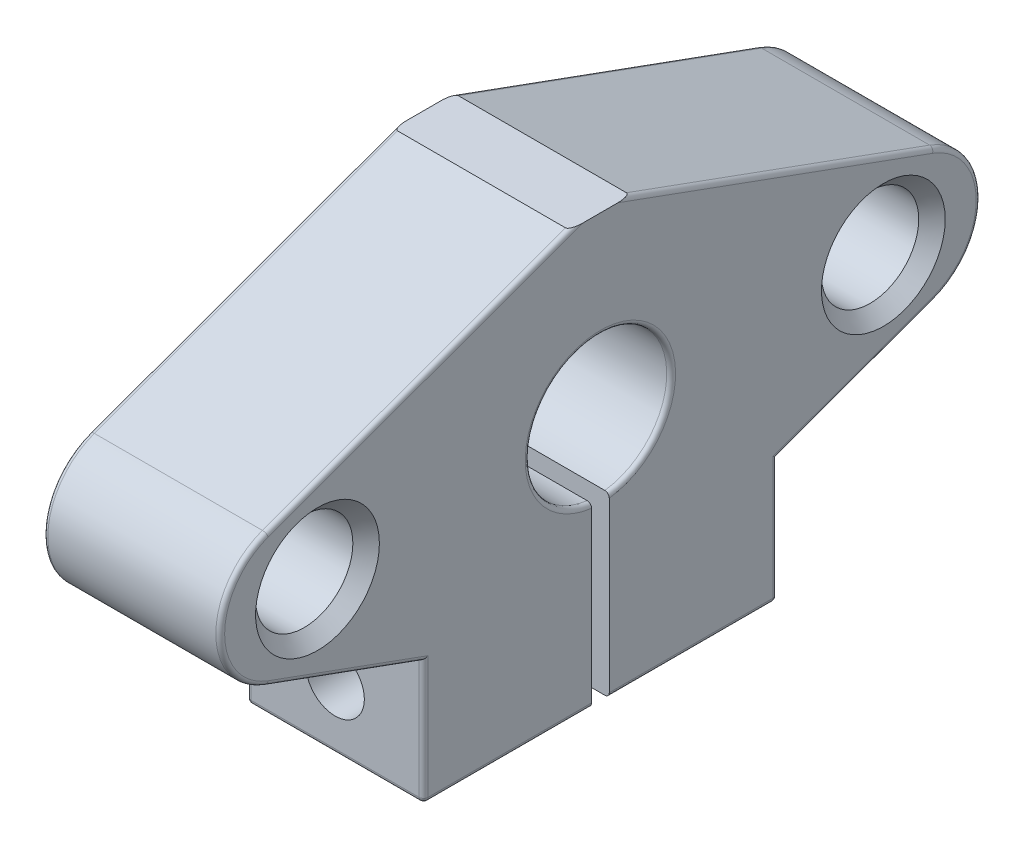
SolidWorks part; units mm, degrees
ref_plane "Plano frontal" through (0, 0, 0) normal (0, 0, 1) x (1, 0, 0)
ref_plane "Plano superior" through (0, 0, 0) normal (0, 1, 0) x (1, 0, 0)
ref_plane "Plano direito" through (0, 0, 0) normal (1, 0, 0) x (0, 0, -1)
sketch "Esboço1" plane through (0, 0, 0) normal (1, 0, 0) x (0, 0, -1)
  line L0 (0, 51.135) -> (0, -31.3516) construction
  line L1 (-77.457, 0) -> (113.3353, 0) construction
  line L2 (1.7204, 24) -> (18.8681, 17.7588)
  line L3 (18.8681, 10.2412) -> (10, 7.0135)
  line L4 (10, 7.0135) -> (10, 0)
  line L5 (-1.7204, 24) -> (1.7204, 24)
  line L6 (21.5, 14) -> (21.5, 29.1302) construction
  line L7 (10, 0) -> (-10, 0)
  line L8 (-1.7204, 24) -> (-18.8681, 17.7588)
  line L9 (-18.8681, 10.2412) -> (-10, 7.0135)
  line L10 (-10, 7.0135) -> (-10, 0)
  circle A0 centre (16, 14) radius 3.5 construction
  arc A1 (18.8681, 17.7588) -> (18.8681, 10.2412) centre (17.5, 14) cw
  arc A2 (-18.8681, 17.7588) -> (-18.8681, 10.2412) centre (-17.5, 14) ccw
  point P18 (0, 24)
  point P23 (0, 0)
  dimension "D3" = 7
  dimension "D4" = 24
  dimension "D7" = 4
  dimension "D1" = 10
  dimension "D2" = 16
  dimension "D5" = 21.5
  dimension "D6" = 40
  dimension "D8" = 10
  dimension "D9" = 10
extrude "Ressalto-extrusão1" add sketch "Esboço1" against normal blind 10
sketch "Esboço2" plane through (0, 0, 0) normal (1, 0, 0) x (0, 0, -1)
  line L0 (0, 28.9047) -> (0, -3.0339) construction
  line L1 (-30.4241, 14) -> (31.1368, 14) construction
  line L2 (-0.5, 10.0314) -> (-0.5, -0.626)
  line L3 (0.5, 10.0314) -> (0.5, -0.626)
  line L4 (-0.5, -0.626) -> (0.5, -0.626)
  arc A0 (0.5, 10.0314) -> (-0.5, 10.0314) centre (0, 14) ccw
  dimension "D1" = 8
  dimension "D2" = 0.5
  dimension "D3" = 0.5
extrude "Corte-extrusão1" cut sketch "Esboço2" against normal blind 10
hole_wizard "Escareado para parafuso de máquina com cabeça chata de M51" positions "Esboço6" profile "Esboço4" countersink size "M5" standard "Ansi Metric" end condition through all
sketch "Esboço6" plane through (0, 0, 0) normal (1, 0, 0) x (0, 0, -1)
  line L0 (0, 14) -> (38.7782, 13.8486) construction
  arc A0 (-18.8681, 17.7588) -> (-18.8681, 10.2412) centre (-17.5, 14) ccw construction
  arc A1 (18.8681, 10.2412) -> (18.8681, 17.7588) centre (17.5, 14) ccw construction
  point P0 (-16, 14.0625)
  point P2 (16, 13.9375)
  point P5 (-21.5, 14)
  point P9 (21.5, 14)
  dimension "D1" = 5.5
  dimension "D2" = 5.5
  dimension "D3" = 0
  dimension "D4" = 0
sketch "Esboço4" plane through (0, 14.0625, 16) normal (0, 1, 0) x (0, 0, -1)
  line L0 (0, 0) -> (0, 10)
  line L1 (0, 10) -> (2.75, 10)
  line L2 (2.75, 10) -> (2.75, 0.75)
  line L3 (2.75, 0.75) -> (3.5, 0)
  line L5 (3.5, 0) -> (0, 0)
  line L6 (-2.75, 0.75) -> (-3.5, 0) construction
  line L11 (0, -6.35) -> (0, 107.95) construction
  dimension "Thru Hole Dia." = 5.5
  dimension "Thru Hole Depth" = 10
  dimension "Near C'Sink Dia." = 7
  dimension "Near C'Sink Angle" = 90
sketch "Esboço7" plane through (0, 0, -10) normal (0, 0, -1) x (-1, 0, 0)
  line L0 (0, 3.5068) -> (10, 3.5068) construction
  line L1 (10, 0) -> (10, 7.0135) construction
  line L2 (0, 0) -> (0, 7.0135) construction
hole_wizard "Broca de rosquear para tarraxa de M4x0.71" positions "Esboço9" profile "Esboço8" hole size "M4x0.7" standard "Ansi Metric" end condition through all
sketch "Esboço9" plane through (0, 0, -10) normal (0, 0, -1) x (-1, 0, 0)
  line L0 (0, 3.5068) -> (10, 3.5068) construction
  point P0 (5, 3.5068)
sketch "Esboço8" plane through (-5, 3.5068, -10) normal (1, 0, 0) x (0, 1, 0)
  line L0 (0, 0) -> (0, 31.5)
  line L1 (0, 31.5) -> (1.65, 31.5)
  line L2 (1.65, 31.5) -> (1.65, 0)
  line L5 (1.65, 0) -> (0, 0)
  line L11 (0, -6.35) -> (0, 107.95) construction
  dimension "Thru Hole Dia." = 3.3
  dimension "Thru Hole Depth" = 31.5
fillet "Filete1" radius 0.25 3 edges at (0, 8.6274, -14.434) (0, 14, -21.5) (0, 20.8794, -10.2943)
fillet "Filete2" radius 0.25 1 edges at (0, 3.6398, -10)
fillet "Filete3" radius 0.25 3 edges at (-5.125, 0, -10) (-0.0732, 0, -9.9268) (0, 0, -5.125)
fillet "Filete4" radius 0.25 3 edges at (-10, 0, 5.25) (-5, 0, 10) (0, 0, 5.25)
fillet "Filete5" radius 0.25 5 edges at (0, 20.8794, 10.2943) (0, 14, 21.5) (-0.0732, 0.0732, 9.9268) (0, 8.6274, 14.434) (0, 3.6318, 10)
fillet "Filete6" radius 0.25 11 edges at (-9.9268, 0.0732, 9.9268) (-10, 8.6274, 14.434) (-10, 14, 21.5) (-10, 20.8794, -10.2943) (-10, 14, -21.5) (-10, 3.6318, -10) (-10, 0.0732, -9.9268) (-10, 3.6318, 10) (-10, 20.8794, 10.2943) (-10, 8.6274, -14.434) (-10, 0, -5.125)
fillet "Filete7" radius 0.25 2 edges at (-10, 18, 0) (0, 18, 0)
